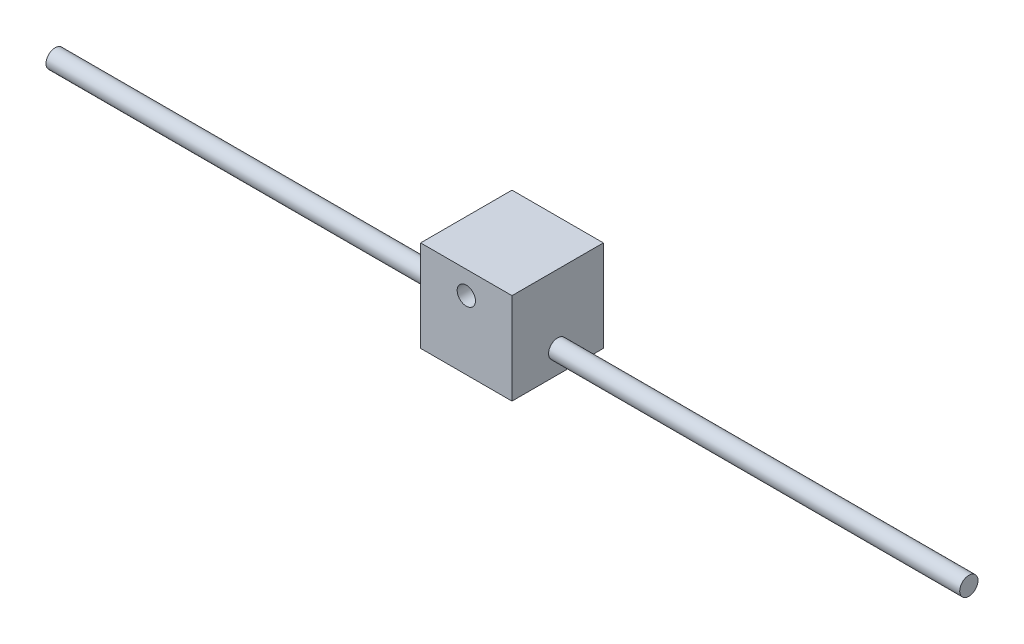
SolidWorks part; units mm, degrees
ref_plane "Plan de face" through (0, 0, 0) normal (0, 0, 1) x (1, 0, 0)
ref_plane "Plan de dessus" through (0, 0, 0) normal (0, 1, 0) x (1, 0, 0)
ref_plane "Plan de droite" through (0, 0, 0) normal (1, 0, 0) x (0, 0, -1)
sketch "Esquisse1" plane through (0, 0, 0) normal (0, 0, 1) x (1, 0, 0)
  line L0 (-20, 0) -> (0, 0) construction
  line L1 (-20, 20) -> (20, 20)
  line L2 (-20, 20) -> (-20, -20)
  line L3 (-20, -20) -> (20, -20)
  line L4 (20, 20) -> (20, -20)
  line L5 (0, 0) -> (0, 20) construction
  circle A0 centre (0, 10) radius 4
  dimension "D2" = 10
  dimension "D3" = 8
  dimension "D1" = 40
extrude "Boss.-Extru.1" add sketch "Esquisse1" along normal mid plane 40
sketch "Esquisse2" plane through (20, 0, 0) normal (1, 0, 0) x (0, 0, -1)
  line L0 (-20, -20) -> (20, -20) construction
  circle A0 centre (0, -10) radius 4
  dimension "D1" = 10
  dimension "D2" = 8
extrude "Enlèv. mat.-Extru.1" cut sketch "Esquisse2" against normal through all
sketch "Esquisse3" plane through (0, 0, 0) normal (1, 0, 0) x (0, 0, -1)
  circle A0 centre (0, -10) radius 4 construction
  circle A1 centre (0, -10) radius 4
extrude "Boss.-Extru.2" add sketch "Esquisse3" along normal mid plane 400 separate body
ref_axis "Axe1" through (200, -10, 0) along (-1, 0, 0)
